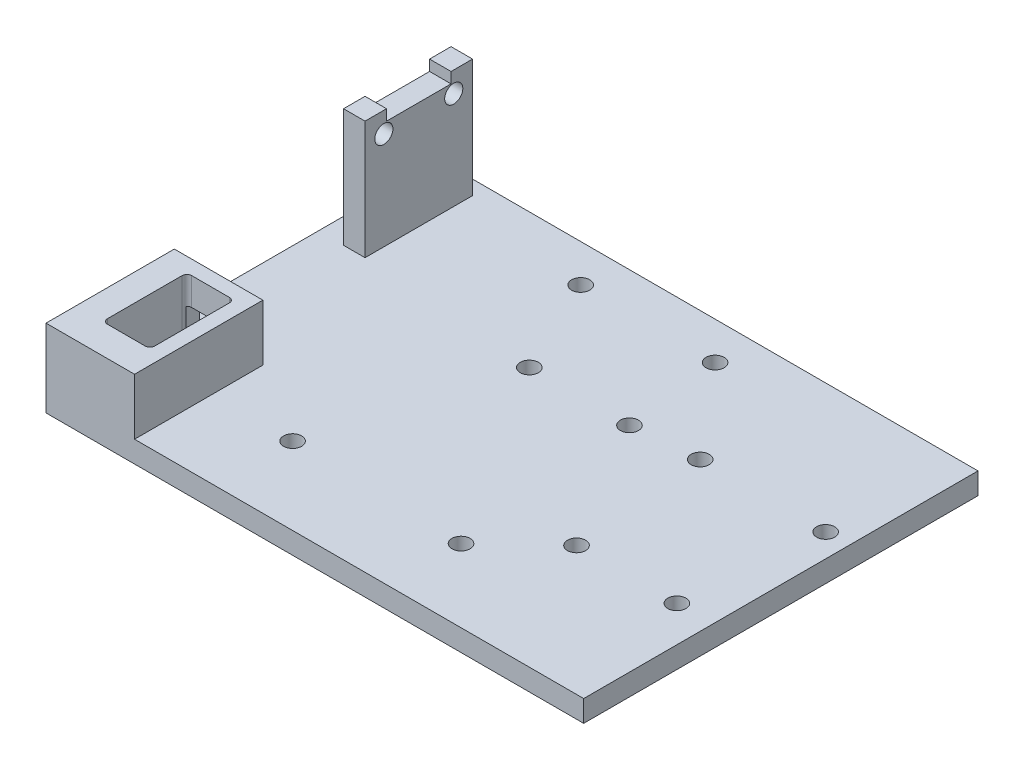
SolidWorks part; units mm, degrees
ref_plane "Front Plane" through (0, 0, 0) normal (0, 0, 1) x (1, 0, 0)
ref_plane "Top Plane" through (0, 0, 0) normal (0, 1, 0) x (1, 0, 0)
ref_plane "Right Plane" through (0, 0, 0) normal (1, 0, 0) x (0, 0, -1)
sketch "Sketch1" plane through (0, 0, 0) normal (0, 1, 0) x (1, 0, 0)
  line L1 (0, 0) -> (150, 0)
  line L2 (0, 0) -> (0, 110)
  line L3 (0, 110) -> (150, 110)
  line L4 (150, 0) -> (150, 110)
  dimension "D1" = 150
  dimension "D2" = 110
extrude "Boss-Extrude1" add sketch "Sketch1" along normal blind 6
hole_wizard "#8 (0.199) Diameter Hole1" positions "Sketch2" profile "Sketch3" hole size "#8" standard "ANSI Inch" end condition up to next
sketch "Sketch2" plane through (0, 6, 0) normal (0, 1, 0) x (1, 0, 0)
  point P0 (90.38, 72.39)
  point P3 (62.44, 72.39)
  point P6 (47.2, 21.59)
  point P9 (95.46, 20.32)
  point P12 (143.5, 74)
  point P15 (108.5, 74)
  point P18 (112, 36)
  point P21 (140, 36)
  point P24 (49.66, 99.5)
  point P27 (87.16, 99.5)
sketch "Sketch3" plane through (90.38, 6, -72.39) normal (1, 0, 0) x (0, 0, 1)
  line L0 (0, 0) -> (0, 6)
  line L1 (0, 6) -> (2.5273, 6)
  line L2 (2.5273, 6) -> (2.5273, 0)
  line L5 (2.5273, 0) -> (0, 0)
  line L11 (0, -6.35) -> (0, 107.95) construction
  dimension "Thru Hole Dia." = 5.0546
  dimension "Thru Hole Depth" = 6
sketch "Sketch4" plane through (0, 6, 0) normal (0, 1, 0) x (1, 0, 0)
  line L0 (150, 110) -> (0, 110) construction
  line L1 (7, 106) -> (13, 106)
  line L2 (7, 106) -> (7, 76)
  line L3 (7, 76) -> (13, 76)
  line L4 (13, 106) -> (13, 76)
  line L5 (0, 110) -> (0, 0) construction
  dimension "D1" = 30
  dimension "D2" = 6
  dimension "D3" = 4
  dimension "D4" = 7
extrude "Boss-Extrude2" add sketch "Sketch4" along normal blind 30
ref_plane "Plane1" through (0, 0, -91) normal (0, 0, -1) x (-1, 0, 0)
hole_wizard "#8 (0.199) Diameter Hole2" positions "Sketch5" profile "Sketch6" hole size "#8" standard "ANSI Inch" end condition up to next
sketch "Sketch5" plane through (7, 0, 0) normal (-1, 0, 0) x (0, 0, 1)
  point P0 (-81.25, 33.27)
  point P3 (-100.75, 33.27)
sketch "Sketch6" plane through (7, 33.27, -81.25) normal (0, 1, 0) x (0, 0, 1)
  line L0 (0, 0) -> (0, 6)
  line L1 (0, 6) -> (2.5273, 6)
  line L2 (2.5273, 6) -> (2.5273, 0)
  line L5 (2.5273, 0) -> (0, 0)
  line L11 (0, -6.35) -> (0, 107.95) construction
  dimension "Thru Hole Dia." = 5.0546
  dimension "Thru Hole Depth" = 6
sketch "Sketch7" plane through (0, 36, 0) normal (0, 1, 0) x (1, 0, 0)
  line L0 (13, 76) -> (13, 106) construction
  line L1 (7, 106) -> (13, 106)
  line L2 (7, 106) -> (7, 100)
  line L3 (7, 100) -> (13, 100)
  line L4 (13, 106) -> (13, 100)
  line L6 (7, 76) -> (13, 76)
  line L7 (7, 76) -> (7, 82)
  line L8 (7, 82) -> (13, 82)
  line L9 (13, 76) -> (13, 82)
  dimension "D1" = 6
  dimension "D2" = 6
extrude "Boss-Extrude3" add sketch "Sketch7" along normal blind 3
sketch "Sketch9" plane through (0, 6, 0) normal (0, 1, 0) x (1, 0, 0)
  line L0 (20.2, 9.65) -> (20.2, 30.45) construction
  line L1 (8.85, 8.8) -> (19.35, 8.8) construction
  line L2 (8, 30.45) -> (8, 9.65) construction
  line L3 (19.35, 31.3) -> (8.85, 31.3) construction
  line L4 (20.2, 9.65) -> (20.2, 30.45) construction
  line L5 (8.85, 8.8) -> (19.35, 8.8) construction
  line L6 (8, 30.45) -> (8, 9.65) construction
  line L7 (19.35, 31.3) -> (8.85, 31.3) construction
  line L8 (20.7, 9.65) -> (20.7, 30.45)
  line L9 (19.35, 31.8) -> (8.85, 31.8)
  line L10 (7.5, 30.45) -> (7.5, 9.65)
  line L11 (8.85, 8.3) -> (19.35, 8.3)
  line L13 (0, 0) -> (24.7, 0)
  line L14 (0, 0) -> (0, 35.8)
  line L15 (0, 35.8) -> (24.7, 35.8)
  line L16 (24.7, 0) -> (24.7, 35.8)
  arc A0 (20.2, 30.45) -> (19.35, 31.3) centre (19.35, 30.45) ccw construction
  arc A1 (19.35, 8.8) -> (20.2, 9.65) centre (19.35, 9.65) ccw construction
  arc A2 (8, 9.65) -> (8.85, 8.8) centre (8.85, 9.65) ccw construction
  arc A3 (8.85, 31.3) -> (8, 30.45) centre (8.85, 30.45) ccw construction
  arc A4 (20.2, 30.45) -> (19.35, 31.3) centre (19.35, 30.45) ccw construction
  arc A5 (19.35, 8.8) -> (20.2, 9.65) centre (19.35, 9.65) ccw construction
  arc A6 (8, 9.65) -> (8.85, 8.8) centre (8.85, 9.65) ccw construction
  arc A7 (8.85, 31.3) -> (8, 30.45) centre (8.85, 30.45) ccw construction
  arc A8 (20.7, 30.45) -> (19.35, 31.8) centre (19.35, 30.45) ccw
  arc A9 (8.85, 31.8) -> (7.5, 30.45) centre (8.85, 30.45) ccw
  arc A10 (7.5, 9.65) -> (8.85, 8.3) centre (8.85, 9.65) ccw
  arc A11 (19.35, 8.3) -> (20.7, 9.65) centre (19.35, 9.65) ccw
  dimension "D2" = 4
  dimension "D3" = 4
  dimension "D1" = 0.5
extrude "Boss-Extrude4" add sketch "Sketch9" along normal blind 15.7
sketch "Sketch10" plane through (0, 0, -35.8) normal (0, 0, -1) x (-1, 0, 0)
  line L0 (-7, 39) -> (-7, 6) construction
  line L1 (-20.7, 6) -> (-7, 6)
  line L2 (-20.7, 6) -> (-20.7, 14)
  line L3 (-20.7, 14) -> (-7, 14)
  line L4 (-7, 6) -> (-7, 14)
  dimension "D1" = 8
extrude "Cut-Extrude1" cut sketch "Sketch10" against normal up to surface (4.5 mm away)
